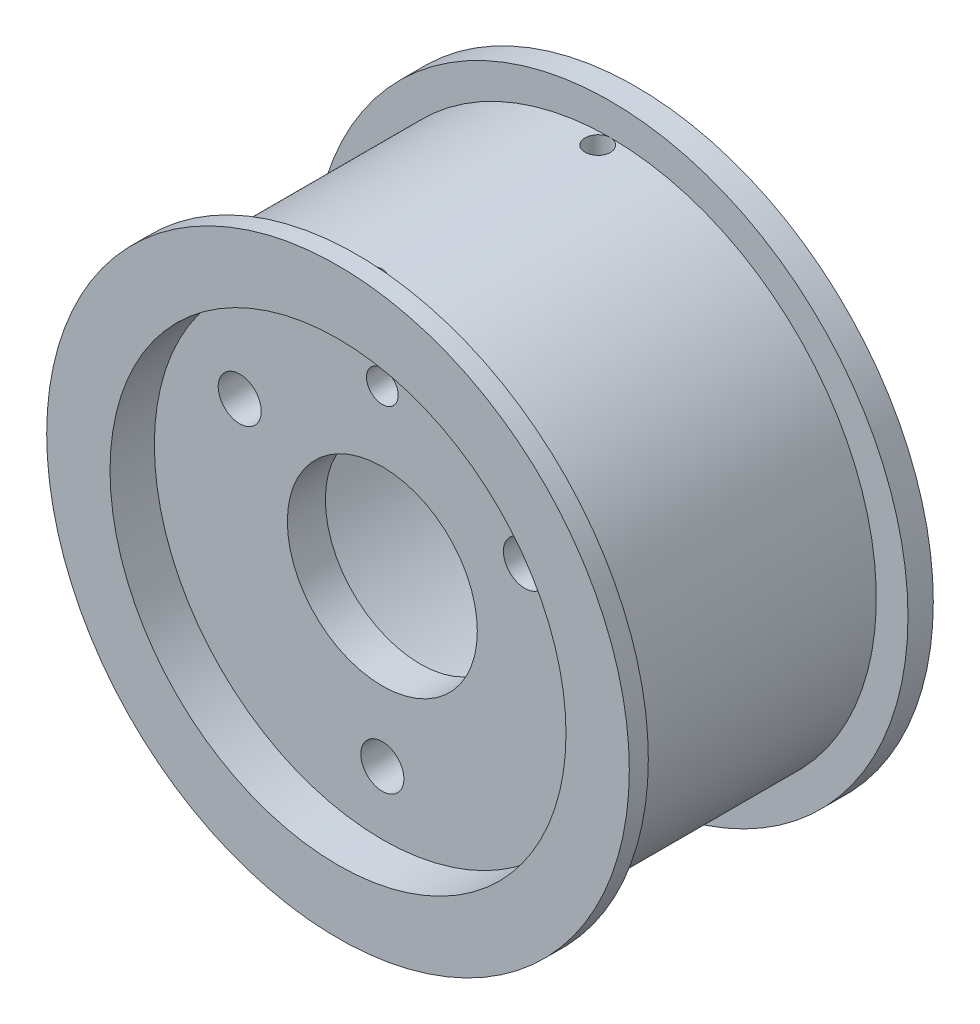
SolidWorks part; units mm, degrees
material "1060 合金"
ref_plane "前视基准面" through (0, 0, 0) normal (0, 0, 1) x (1, 0, 0)
ref_plane "上视基准面" through (0, 0, 0) normal (0, 1, 0) x (1, 0, 0)
ref_plane "右视基准面" through (0, 0, 0) normal (1, 0, 0) x (0, 0, -1)
sketch "草图1" plane through (0, 0, 0) normal (1, 0, 0) x (0, 0, -1)
  line L0 (-11.75, 0) -> (-11.75, 48.2279) construction
  line L1 (-11.75, 0) -> (75.147, 0) construction
  line L2 (0, 21) -> (0, -6.6133) construction
  line L3 (-11.75, 21) -> (-11.75, 18)
  line L4 (-8.25, 7.5) -> (-8.25, 18)
  line L5 (-11.75, 21) -> (11.75, 21)
  line L6 (11.75, 18) -> (11.75, 21)
  line L7 (-11.75, 18) -> (-8.25, 18)
  line L9 (11.75, 18) -> (-5.25, 18)
  line L10 (-5.25, 7.5) -> (-5.25, 18)
  line L13 (-5.25, 7.5) -> (-8.25, 7.5)
  dimension "D1" = 7.5
  dimension "D2" = 3
  dimension "D3" = 18
  dimension "D4" = 3
  dimension "D5" = 23.5
  dimension "D6" = 3.5
revolve "旋转1" add sketch "草图1" angle 360 about L1
hole_wizard "M3 间隙孔1" positions "草图3" profile "草图2" hole size "M3" standard "GB"
sketch "草图3" plane through (0, 0, 8.25) normal (0, 0, 1) x (1, 0, 0)
  line L0 (0, 0) -> (24.1812, 13.961) construction
  line L1 (0, 0) -> (0, 29.0656) construction
  circle A0 centre (0, 0) radius 13 construction
  point P0 (11.2583, 6.5)
  point P24 (0, -13)
  point P25 (-11.2583, 6.5)
  dimension "D1" = 26
  dimension "D3" = 60
  dimension "D2" = 3
sketch "草图2" plane through (11.2583, 6.5, 8.25) normal (1, 0, 0) x (0, -1, 0)
  line L0 (0, 0) -> (0, 24.0215)
  line L1 (0, 24.0215) -> (1.7, 23)
  line L2 (1.7, 23) -> (1.7, 0)
  line L5 (1.7, 0) -> (0, 0)
  line L10 (0, 24.0215) -> (-1.7, 23) construction
  line L11 (0, -6.35) -> (0, 107.95) construction
  dimension "孔直径" = 3.4
  dimension "孔深度" = 23
  dimension "导头角度" = 118
sketch "草图8" plane through (0, 0, 0) normal (0, 0, 1) x (1, 0, 0)
  circle A0 centre (0, 0) radius 26
  dimension "D1" = 52
extrude "凸台-拉伸1" [suppressed] add sketch "草图8" along normal mid plane 20 separate body
sketch "草图4" plane through (0, 0, 0) normal (0, 1, 0) x (1, 0, 0)
  line L0 (0, -10.5473) -> (0, 33.1049) construction
  line L2 (21, -11.75) -> (23, -11.75)
  line L3 (21, -11.75) -> (21, -10.25)
  line L4 (21, -10.25) -> (23, -10.25)
  line L5 (23, -11.75) -> (23, -10.25)
  line L6 (21, 11.75) -> (23.5, 11.75)
  line L7 (21, 11.75) -> (21, 9.75)
  line L8 (21, 9.75) -> (23.5, 9.75)
  line L9 (23.5, 11.75) -> (23.5, 9.75)
  dimension "D1" = 2
  dimension "D2" = 2.5
  dimension "D3" = 1.5
  dimension "D4" = 2
revolve "台阶" add sketch "草图4" angle 360 about L0
sketch "草图6" plane through (0, 0, 0) normal (0, 1, 0) x (1, 0, 0)
  line L2 (23, -10.25) -> (-23, -10.25) construction
  line L3 (23, -10.25) -> (-23, -10.25) construction
  line L4 (-23.5, 9.75) -> (23.5, 9.75) construction
  line L5 (-23.5, 9.75) -> (23.5, 9.75) construction
  line L7 (0, 14.3969) -> (0, -17.7582) construction
  circle A0 centre (0, 8.75) radius 1
  circle A1 centre (0, -9.25) radius 1
  dimension "D1" = 2
  dimension "D2" = 2
extrude "切除-拉伸1" cut sketch "草图6" along normal through all
sketch "草图7" plane through (0, 0, 8.25) normal (0, 0, 1) x (1, 0, 0)
  line L0 (0, 27.5413) -> (0, -29.9529) construction
  line L1 (-34.8705, 0) -> (0, 0) construction
  circle A0 centre (0, 17) radius 1
  circle A1 centre (0, 0) radius 18 construction
  circle A2 centre (0, 0) radius 18 construction
  point P11 (0, 18)
  dimension "D1" = 2
  dimension "D2" = 1
extrude "切除-拉伸2" cut sketch "草图7" against normal through all
pattern_circular "阵列(圆周)1" [suppressed] count 3 over 360 of bodies 110
sketch "草图5" plane through (0, 0, 0) normal (0, 1, 0) x (1, 0, 0)
  line L0 (21, -10.25) -> (21, 9.75) construction
  line L1 (-23.5, 9.75) -> (23.5, 9.75) construction
  line L2 (0, 0) -> (0, 30.1002) construction
  circle A0 centre (23.5, 7.25) radius 2.5
  dimension "D1" = 5
revolve "旋转3" [suppressed] add sketch "草图5" angle 360 about L2
pattern_linear "阵列(线性)2" [suppressed] count 4 spacing 5 of bodies 105
sketch "草图9" plane through (0, 0, 0) normal (1, 0, 0) x (0, 0, -1)
  circle A0 centre (-8.5, 23.5) radius 2.5
  circle A1 centre (-8.5, 23.5) radius 1
  point P2 (-10.5, 22)
  dimension "D1" = 5
  dimension "D3" = 2
  dimension "D2" = 23.5
ref_plane "基准面1" through (0, 0, 8.5) normal (0, 0, 1) x (1, 0, 0)
sketch "草图10" plane through (0, 0, 8.5) normal (0, 0, 1) x (1, 0, 0)
  circle A0 centre (0, 0) radius 23.5
hole_wizard "M3 螺纹孔1" positions "草图12" profile "草图11" tap size "M3" standard "GB" end condition through all
sketch "草图12" plane through (0, 0, 8.25) normal (0, 0, 1) x (1, 0, 0)
  point P0 (0, 13)
  dimension "D1" = 13
sketch "草图11" plane through (0, 13, 8.25) normal (1, 0, 0) x (0, -1, 0)
  line L0 (0, 0) -> (0, 20)
  line L1 (0, 20) -> (1.25, 20)
  line L2 (1.25, 20) -> (1.25, 0)
  line L5 (1.25, 0) -> (0, 0)
  line L11 (0, -6.35) -> (0, 107.95) construction
  dimension "通孔螺纹孔钻头直径" = 2.5
  dimension "通孔螺纹孔钻头深度" = 20
cosmetic thread "孔螺蚊线1" parameters "D2"=3
move or copy body "实体-移动/复制1" [suppressed] bodies to move or copy 105 106 107 108 111 112
